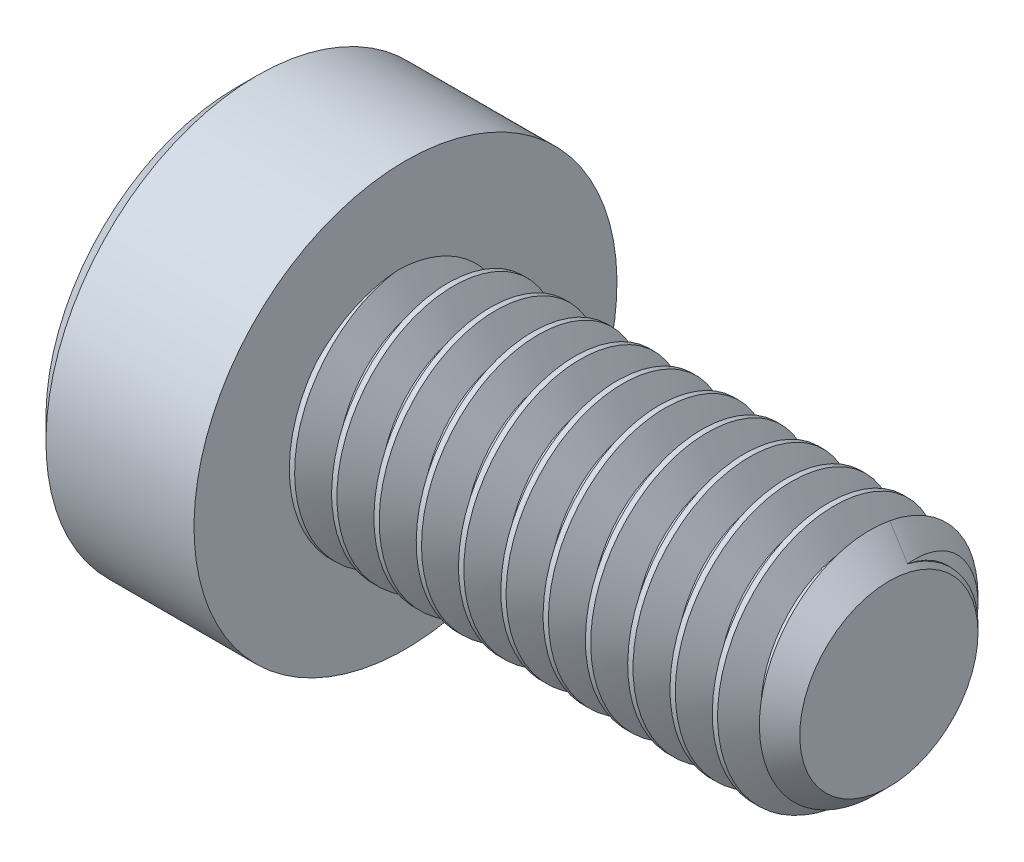
SolidWorks part; units mm, degrees
ref_plane "Front Plane" through (0, 0, 0) normal (0, 0, 1) x (1, 0, 0)
ref_plane "Top Plane" through (0, 0, 0) normal (0, 1, 0) x (1, 0, 0)
ref_plane "Right Plane" through (0, 0, 0) normal (1, 0, 0) x (0, 0, -1)
sketch "Sketch1" plane through (0, 0, 0) normal (0, 0, 1) x (1, 0, 0)
  line L0 (4, 0) -> (-4, 0) construction
  line L1 (4, 2) -> (4, -2) construction
  line L2 (-4, 3.5) -> (-4, -3.5) construction
  line L3 (-4, 3.5) -> (-6.45, 3.5) construction
  line L4 (-6.45, 3.5) -> (-6.8, 3.15) construction
  line L5 (-6.8, 3.15) -> (-6.8, -3.15) construction
  line L6 (-6.8, -3.15) -> (-6.45, -3.5) construction
  line L7 (-6.45, -3.5) -> (-4, -3.5) construction
  point P7 (-4.38, 0)
  point P12 (1.2, -2)
  dimension "D1" = 45
  dimension "Dec." = 4
  dimension "Length" = 8
  dimension "Head Dia" = 7
  dimension "Head Height" = 2.8
  dimension "Hex Depth" = 2.42
  dimension "Chamfer" = 0.35
  dimension "D2" = 2.8
ref_plane "Plane1" through (4, 0, 0) normal (1, 0, 0) x (0, 0, -1)
ref_plane "Plane2" through (-6.8, 0, 0) normal (1, 0, 0) x (0, 0, -1)
sketch "Sketch2" plane through (4, 0, 0) normal (1, 0, 0) x (0, 0, -1)
  circle A0 centre (0, 0) radius 2
extrude "Boss-Extrude1" add sketch "Sketch2" against normal up to vertex (8 mm away) up to point (-4, 0, 0)
sketch "Sketch3" plane through (4, 0, 0) normal (1, 0, 0) x (0, 0, -1)
  circle A0 centre (0, 0) radius 2 construction
  circle A1 centre (0, 0) radius 2
curve "Helix/Spiral1" pitch 0.7 height 8.7 radius 2 centre (4, 0, 0) axis (-1, 0, 0) start towards (0, 1, 0) parameters "Pitch"=0.7
chamfer "Chamfer1" distance 0.525 angle 45 1 edges at (4, 0, -2)
sketch "Sketch5" plane through (0, 0, 0) normal (0, 0, 1) x (1, 0, 0)
  line L0 (3.6938, 2) -> (4.3062, 2)
  line L1 (4.3062, 2) -> (4.0437, 1.5453)
  line L2 (4.0437, 1.5453) -> (3.9562, 1.5453)
  line L3 (3.9562, 1.5453) -> (3.6938, 2)
  line L4 (4, 1.5453) -> (4, 2) construction
  line L5 (3.825, 1.7727) -> (4.175, 1.7727) construction
  dimension "D1" = 60
  dimension "D2" = 0.35
  dimension "D3" = 0.0875
sweep "Cut-Sweep1" cut profiles "Sketch5" path "Helix/Spiral1" align with end faces yes
sketch "Sketch4" plane through (-6.8, 0, 0) normal (1, 0, 0) x (0, 0, -1)
  line L0 (-3.5, 0.7937) -> (3.5, 0.7937) construction
  line L1 (0, 1.4434) -> (-1.25, 0.7217)
  line L2 (-1.25, 0.7217) -> (-1.25, -0.7217)
  line L3 (-1.25, -0.7217) -> (0, -1.4434)
  line L4 (0, -1.4434) -> (1.25, -0.7217)
  line L5 (1.25, -0.7217) -> (1.25, 0.7217)
  line L6 (1.25, 0.7217) -> (0, 1.4434)
  line L7 (0, 0) -> (0, 0.7937) construction
  circle A0 centre (0, 0) radius 1.25 construction
  dimension "Hex Size" = 2.5
  dimension "D1" = 7
  dimension "D2" = 0.7937
sketch "Sketch6" plane through (0, 0, 0) normal (0, 0, 1) x (1, 0, 0)
  line L0 (-6.45, 3.5) -> (-6.8, 3.15) construction
  line L1 (-4, 3.5) -> (-6.45, 3.5) construction
  line L2 (-4, 3.5) -> (-4, -3.5) construction
  line L3 (-6.8, 3.15) -> (-6.8, -3.15) construction
  line L4 (-6.45, 3.5) -> (-6.8, 3.15)
  line L5 (-4, 3.5) -> (-6.45, 3.5)
  line L6 (-4, 3.5) -> (-4, 0)
  line L7 (-6.8, 3.15) -> (-6.8, 0)
  line L8 (-4, 0) -> (-6.8, 0) construction
  line L9 (-4, 0) -> (-6.8, 0)
revolve "Revolve1" add sketch "Sketch6" angle 360 about L8
extrude "Cut-Extrude1" cut sketch "Sketch4" along normal up to vertex (2.42 mm away) up to point (-4.38, 0, 0)
sketch "Sketch8" plane through (-6.8, 0, 0) normal (-1, 0, 0) x (0, 0, 1)
  circle A1 centre (0, 0) radius 1.4434
extrude "Cut-Extrude2" cut sketch "Sketch8" against normal through all draft 45
move or copy body "Body-Move/Copy1" [suppressed] bodies to move or copy 105
equation "\"D3@Helix/Spiral1\" = \"Length@Sketch1\"+\"Pitch@Helix/Spiral1\""
equation "\"D3@Sketch5\" = \"Pitch@Helix/Spiral1\"*.125"
equation "\"D2@Sketch5\" = \"Pitch@Helix/Spiral1\"*.50"
equation "\"D1@Chamfer1\" = \"Pitch@Helix/Spiral1\"*.75"
equation "\"D2@Sketch1\" = \"Pitch@Helix/Spiral1\"*4"
equation "\"D1@Sketch4\" = \"Head Dia@Sketch1\""
equation "\"Chamfer@Sketch1\" = \"Head Height@Sketch1\"/8"
